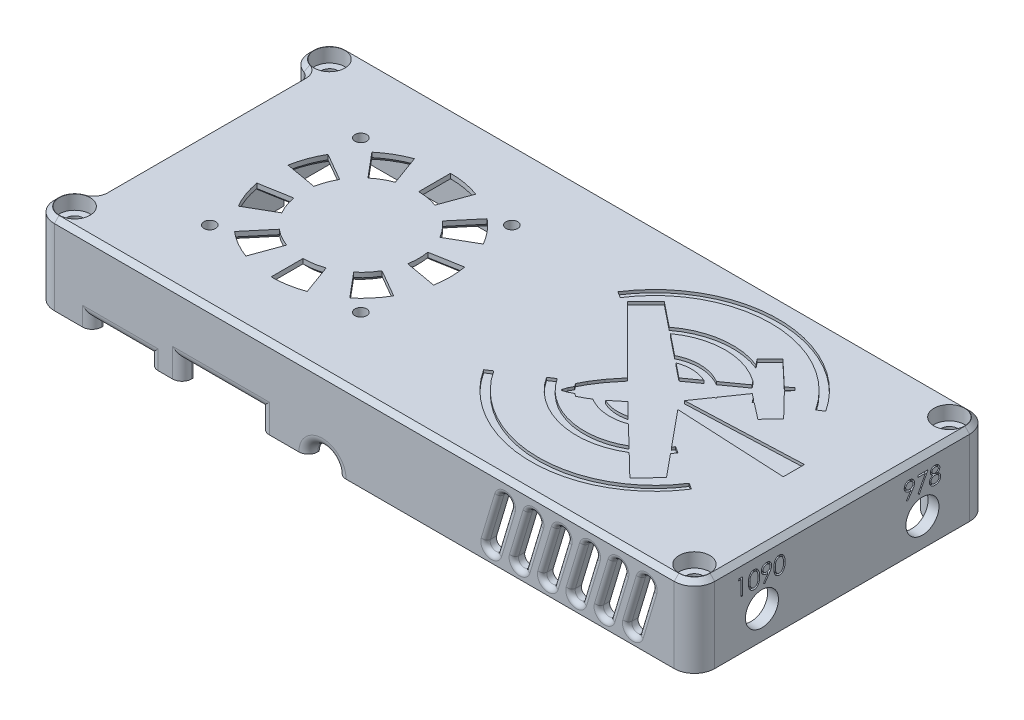
SolidWorks part; units mm, degrees
ref_plane "Front Plane" through (0, 0, 0) normal (0, 0, 1) x (1, 0, 0)
ref_plane "Top Plane" through (0, 0, 0) normal (0, 1, 0) x (1, 0, 0)
ref_plane "Right Plane" through (0, 0, 0) normal (1, 0, 0) x (0, 0, -1)
sketch "Sketch1" plane through (0, 0, 0) normal (0, 1, 0) x (1, 0, 0)
  line L0 (-71.5618, 3.106) -> (57.4382, 3.106) construction
  line L1 (-71.5618, 31.106) -> (57.4382, 31.106)
  line L2 (-71.5618, 31.106) -> (-71.5618, -24.894)
  line L3 (-71.5618, -24.894) -> (57.4382, -24.894)
  line L4 (57.4382, 31.106) -> (57.4382, -24.894)
  line L5 (-60.6618, -24.894) -> (-60.6618, -31.6828) construction
  line L6 (-68.0618, 27.606) -> (-10.0618, 27.606)
  line L7 (-68.0618, 27.606) -> (-68.0618, -21.394)
  line L8 (-68.0618, -21.394) -> (-10.0618, -21.394)
  line L9 (-10.0618, 27.606) -> (-10.0618, -21.394)
  line L10 (-39.5618, -24.894) -> (-39.5618, -31.6828) construction
  line L11 (-18.0618, -24.894) -> (-18.0618, -31.6828) construction
  line L12 (-65.4118, -26.5648) -> (-55.9118, -26.5648) construction
  line L13 (-48.0618, -26.5648) -> (-31.0618, -26.5648) construction
  line L14 (-22.0618, -26.5648) -> (-14.0618, -26.5648) construction
  line L15 (-72.5618, 9.606) -> (-72.5618, -3.394) construction
  line L16 (-71.5618, 3.106) -> (-72.5618, 3.106) construction
  line L17 (-60.6618, -24.894) -> (-60.6618, 40.2849) construction
  dimension "D1" = 129
  dimension "D2" = 56
  dimension "D3" = 49
  dimension "D4" = 58
  dimension "D5" = 3.5
  dimension "D6" = 3.5
  dimension "D7" = 10.9
  dimension "D8" = 32
  dimension "D9" = 53.5
  dimension "D10" = 2
  dimension "D11" = 13
  dimension "D12" = 9.5
  dimension "D13" = 17
  dimension "D14" = 8
sketch "Sketch3" plane through (0, 0, 0) normal (0, 1, 0) x (1, 0, 0)
  line L2 (-72.5618, -25.894) -> (58.4382, -25.894) construction
  line L3 (60.7382, -28.194) -> (60.7382, 34.406) construction
  line L4 (60.7382, 34.406) -> (-74.8618, 34.406)
  line L5 (-74.8618, 34.406) -> (-74.8618, -28.194)
  line L6 (-74.8618, -28.194) -> (60.7382, -28.194)
  line L8 (58.4382, 32.106) -> (-72.5618, 32.106)
  line L9 (58.4382, -25.894) -> (58.4382, 32.106)
  line L10 (-72.5618, -25.894) -> (58.4382, -25.894)
  line L11 (-72.5618, 32.106) -> (-72.5618, -25.894)
  line L12 (58.4382, 32.106) -> (-72.5618, 32.106)
  line L13 (58.4382, -25.894) -> (58.4382, 32.106)
  line L14 (-72.5618, -25.894) -> (58.4382, -25.894)
  line L15 (-72.5618, 32.106) -> (-72.5618, -25.894)
  line L16 (-7.0618, 3.106) -> (-7.0618, 34.406) construction
  line L17 (-71.5618, 3.106) -> (57.4382, 3.106) construction
  line L18 (58.4382, -25.894) -> (58.4382, 32.106) construction
  line L20 (-74.8618, 3.106) -> (52.7382, 3.106) construction
  line L22 (-74.8618, -28.194) -> (60.7382, -28.194) construction
  line L23 (60.7382, -28.194) -> (60.7382, 34.406)
  dimension "D1" = 1
  dimension "D2" = 2.3
extrude "Boss-Extrude1" add sketch "Sketch3" along normal blind 17
sketch "Sketch5" plane through (0, 0, 0) normal (0, 1, 0) x (1, 0, 0)
  line L1 (-72.5618, 32.106) -> (58.4382, 32.106)
  line L2 (-72.5618, 32.106) -> (-72.5618, -25.894)
  line L3 (-72.5618, -25.894) -> (58.4382, -25.894)
  line L4 (58.4382, 32.106) -> (58.4382, -25.894)
sketch "Sketch11" plane through (0, 0, 28.194) normal (0, 0, 1) x (1, 0, 0)
  line L0 (-74.8618, 17) -> (-74.8618, 0) construction
  line L2 (-66.8618, 0) -> (-54.8618, 0)
  line L3 (-66.8618, 0) -> (-66.8618, 2)
  line L4 (-66.8618, 2) -> (-54.8618, 2)
  line L5 (-54.8618, 0) -> (-54.8618, 2)
  line L9 (-47.8118, 4) -> (-31.3118, 4)
  line L10 (-47.8118, 4) -> (-47.8118, 0)
  line L11 (-47.8118, 0) -> (-31.3118, 0)
  line L12 (-31.3118, 4) -> (-31.3118, 0)
  line L14 (-39.5618, 0) -> (-39.528, 10.3) construction
  line L15 (-48.0618, 0) -> (-31.0618, 0) construction
  line L16 (-18.0618, 0) -> (-18.0618, 10.3) construction
  line L17 (-22.0618, 0) -> (-14.0618, 0) construction
  circle A0 centre (-18.0618, 0) radius 3
  dimension "D5" = 6
  dimension "D1" = 4
  dimension "D2" = 2
  dimension "D3" = 12
  dimension "D4" = 16.5
  dimension "D7" = 8
extrude "Cut-Extrude1" cut sketch "Sketch11" against normal up to next
sketch "Sketch14" plane through (0, 0, 0) normal (0, -1, 0) x (1, 0, 0)
  line L1 (-74.8618, 11.894) -> (-72.5618, 11.894)
  line L2 (-74.8618, 11.894) -> (-74.8618, -18.106)
  line L3 (-74.8618, -18.106) -> (-72.5618, -18.106)
  line L4 (-72.5618, 11.894) -> (-72.5618, -18.106)
  dimension "D1" = 30
extrude "Boss-Extrude6" add sketch "Sketch14" along normal blind 2.8
fillet "Fillet6" radius 2 4 edges at (-18.0618, 3, 28.194) (-31.3118, 2, 28.194) (-39.5618, 4, 28.194) (-47.8118, 2, 28.194)
sketch "Sketch15" plane through (-74.8618, 0, 0) normal (-1, 0, 0) x (0, 0, 1)
  line L1 (-9.7403, -3.6489) -> (3.7597, -3.6489)
  line L2 (-9.7403, -3.6489) -> (-9.7403, -2.6489)
  line L3 (-9.7403, -2.6489) -> (3.7597, -2.6489)
  line L4 (3.7597, -3.6489) -> (3.7597, -2.6489)
extrude "Cut-Extrude3" cut sketch "Sketch15" against normal up to next
fillet "Fillet8" radius 2 3 edges at (-74.8618, -2.7245, 3.7597) (-74.8618, -2.7245, -9.7403) (-74.8618, -2.6489, -2.9903)
sketch "Sketch35" plane through (0, 17, 0) normal (0, 1, 0) x (1, 0, 0)
  line L1 (-72.5618, 32.106) -> (58.4382, 32.106)
  line L2 (-72.5618, 32.106) -> (-72.5618, -25.894)
  line L3 (-72.5618, -25.894) -> (58.4382, -25.894)
  line L4 (58.4382, 32.106) -> (58.4382, -25.894)
extrude "Boss-Extrude7" add sketch "Sketch35" against normal blind 2
sketch "Sketch36" plane through (0, 17, 0) normal (0, 1, 0) x (1, 0, 0)
  line L0 (13.7863, -0.484) -> (12.349, -1.4216)
  line L1 (26.8986, -0.4563) -> (28.3399, -1.3879)
  line L2 (13.7684, 8.0304) -> (12.3271, 8.962)
  line L3 (26.8807, 8.058) -> (28.318, 8.9957)
  line L4 (41.0203, -9.5839) -> (42.3245, -10.4269)
  line L5 (32.8559, -4.3068) -> (34.2397, -5.2013)
  line L6 (7.8454, -4.3595) -> (6.4653, -5.2598)
  line L7 (-0.2967, -9.6709) -> (-1.5974, -10.5194)
  line L8 (-0.3532, 17.158) -> (-1.6575, 18.001)
  line L9 (7.8112, 11.8809) -> (6.4273, 12.7754)
  line L10 (32.8217, 11.9336) -> (34.2017, 12.8338)
  line L11 (40.9638, 17.245) -> (42.2645, 18.0935)
  line L12 (49.7971, 1.5668) -> (22.6747, 2.9133)
  line L13 (49.7971, 6.0552) -> (22.6747, 4.9652)
  line L14 (49.7971, 1.5668) -> (49.7971, 6.0552)
  line L15 (22.6747, 2.9133) -> (22.6747, 4.9652)
  arc A0 (42.2645, 18.0935) -> (-1.6575, 18.001) centre (20.3335, 3.787) ccw
  arc A1 (40.9638, 17.245) -> (-0.3532, 17.158) centre (20.3335, 3.787) ccw
  arc A2 (26.8807, 8.058) -> (13.7684, 8.0304) centre (20.3335, 3.787) ccw
  arc A3 (28.318, 8.9957) -> (12.3271, 8.962) centre (20.3335, 3.787) ccw
  arc A4 (34.2017, 12.8338) -> (6.4273, 12.7754) centre (20.3335, 3.787) ccw
  arc A5 (32.8217, 11.9336) -> (7.8112, 11.8809) centre (20.3335, 3.787) ccw
  arc A6 (-1.5974, -10.5194) -> (42.3245, -10.4269) centre (20.3335, 3.787) ccw
  arc A7 (-0.2967, -9.6709) -> (41.0203, -9.5839) centre (20.3335, 3.787) ccw
  arc A8 (6.4653, -5.2598) -> (34.2397, -5.2013) centre (20.3335, 3.787) ccw
  arc A9 (7.8454, -4.3595) -> (32.8559, -4.3068) centre (20.3335, 3.787) ccw
  arc A10 (12.349, -1.4216) -> (28.3399, -1.3879) centre (20.3335, 3.787) ccw
  arc A11 (13.7863, -0.484) -> (26.8986, -0.4563) centre (20.3335, 3.787) ccw
extrude "Cut-Extrude4" cut sketch "Sketch36" against normal blind 0.6
sketch "Sketch37" plane through (0, 17, 0) normal (0, 1, 0) x (1, 0, 0)
  line L0 (19.5432, -1.113) -> (33.7651, -14.904)
  line L1 (33.7651, -14.904) -> (37.5849, -10.9649)
  line L2 (37.5849, -10.9649) -> (24.9049, 4.4162)
  line L3 (24.9049, 4.4162) -> (31.2449, 13.5399)
  line L4 (31.2449, 13.5399) -> (36.5589, 9.4198)
  line L5 (36.5589, 9.4198) -> (39.2481, 12.193)
  line L6 (39.2481, 12.193) -> (34.218, 17.3746)
  line L7 (34.218, 17.3746) -> (35.2171, 18.6632)
  line L8 (35.2171, 18.6632) -> (34.9302, 18.8856)
  line L9 (19.5432, -1.113) -> (16.9215, -3.2743)
  line L10 (16.9215, -3.2743) -> (14.6893, -4.7957)
  line L11 (14.6893, -4.7957) -> (13.0543, -5.6738)
  line L12 (13.0543, -5.6738) -> (12.4225, -5.2348)
  line L13 (12.4225, -5.2348) -> (11.4673, -5.7477)
  line L14 (11.4673, -5.7477) -> (10.605, -6.0351)
  line L15 (10.605, -6.0351) -> (10.3641, -6.0351)
  line L16 (34.9302, 18.8856) -> (10.3641, -6.0351) construction
  line L17 (10.3607, -5.7943) -> (10.3641, -6.0351)
  line L18 (10.6357, -4.9279) -> (10.3607, -5.7943)
  line L19 (11.1349, -3.9655) -> (10.6357, -4.9279)
  line L20 (10.6869, -3.3401) -> (11.1349, -3.9655)
  line L21 (11.5414, -1.6927) -> (10.6869, -3.3401)
  line L22 (13.0306, 0.5611) -> (11.5414, -1.6927)
  line L23 (15.1541, 3.2135) -> (13.0306, 0.5611)
  line L24 (34.7036, 19.1694) -> (34.9302, 18.8856)
  line L25 (33.4295, 18.1519) -> (34.7036, 19.1694)
  line L26 (28.1763, 23.1072) -> (33.4295, 18.1519)
  line L27 (25.4419, 20.3785) -> (28.1763, 23.1072)
  line L28 (29.6378, 15.1241) -> (25.4419, 20.3785)
  line L29 (20.6059, 8.6539) -> (29.6378, 15.1241)
  line L30 (5.0446, 21.1121) -> (20.6059, 8.6539)
  line L31 (1.1607, 17.2363) -> (5.0446, 21.1121)
  line L32 (15.1541, 3.2135) -> (1.1607, 17.2363)
extrude "Cut-Extrude5" cut sketch "Sketch37" against normal blind 0.6
sketch "Sketch48" plane through (0, 17, 0) normal (0, 1, 0) x (1, 0, 0)
  line L0 (-74.8618, -19.594) -> (-74.8618, -28.194)
  line L1 (-74.8618, 34.406) -> (-74.8618, 25.806)
  line L2 (-74.8618, 3.106) -> (-35.5735, 3.106) construction
  line L3 (-74.8618, 34.406) -> (-74.8618, -28.194) construction
  line L4 (60.7382, -28.194) -> (60.7382, 34.406) construction
  arc A0 (-74.8618, -28.194) -> (-74.8618, -19.594) centre (-74.8618, -23.894) cw
  arc A1 (-74.8618, 25.806) -> (-74.8618, 34.406) centre (-74.8618, 30.106) cw
  circle A2 centre (56.4382, 30.106) radius 4.3
  circle A3 centre (56.4382, -23.894) radius 4.3
  dimension "D1" = 4.3
extrude "Boss-Extrude9" add sketch "Sketch48" against normal up to vertex (17 mm away) up to point (-74.8618, 0, -34.406)
hole_wizard "CBORE for M3 SHCS1" positions "Sketch50" profile "Sketch49" counterbore size "M3" standard "ANSI Metric" end condition up to next
sketch "Sketch50" plane through (0, 17, 0) normal (0, 1, 0) x (1, 0, 0)
  point P0 (-74.8618, 30.106)
sketch "Sketch49" plane through (-74.8618, 17, -30.106) normal (1, 0, 0) x (0, 0, 1)
  line L0 (0, 0) -> (0, 17)
  line L1 (0, 17) -> (1.8, 17)
  line L3 (1.8, 17) -> (1.8, 3)
  line L4 (1.8, 3) -> (3.25, 3)
  line L5 (3.25, 3) -> (3.25, 0)
  line L7 (3.25, 0) -> (0, 0)
  line L11 (0, -6.35) -> (0, 107.95) construction
  dimension "Thru Hole Dia." = 3.6
  dimension "Thru Hole Depth" = 17
  dimension "C'Bore Dia." = 6.5
  dimension "C'Bore Depth" = 3
hole_wizard "CBORE for M3 SHCS2" positions "Sketch52" profile "Sketch51" counterbore size "M3" standard "ANSI Metric" end condition up to next
sketch "Sketch52" plane through (0, 17, 0) normal (0, 1, 0) x (1, 0, 0)
  point P0 (-74.8618, -23.894)
sketch "Sketch51" plane through (-74.8618, 17, 23.894) normal (1, 0, 0) x (0, 0, 1)
  line L0 (0, 0) -> (0, 17)
  line L1 (0, 17) -> (1.8, 17)
  line L3 (1.8, 17) -> (1.8, 3)
  line L4 (1.8, 3) -> (3.25, 3)
  line L5 (3.25, 3) -> (3.25, 0)
  line L7 (3.25, 0) -> (0, 0)
  line L11 (0, -6.35) -> (0, 107.95) construction
  dimension "Thru Hole Dia." = 3.6
  dimension "Thru Hole Depth" = 17
  dimension "C'Bore Dia." = 6.5
  dimension "C'Bore Depth" = 3
fillet "Fillet13" radius 2 2 edges at (-74.8618, 8.5, 19.594) (-74.8618, 8.5, -25.806)
chamfer "Chamfer1" distance 1 angle 45 1 edges at (-9.8342, 15, -32.106)
chamfer "Chamfer3" distance 1 angle 45 7 edges at (-7.0618, 17, 28.194) (-79.1058, 17, 24.5855) (-75.2385, 17, 19.0883) (-74.8618, 17, -3.106) (-75.2385, 17, -25.3002) (-79.1058, 17, -30.7975) (-7.0618, 17, -34.406)
fillet "Fillet14" radius 2 3 edges at (-66.8618, 1, 28.194) (-60.8618, 2, 28.194) (-54.8618, 1, 28.194)
fillet "Fillet15" radius 4.3 2 edges at (60.7382, 8, -34.406) (60.7382, 8, 28.194)
hole_wizard "CBORE for M3 SHCS4" positions "Sketch62" profile "Sketch61" counterbore size "M3" standard "ANSI Metric" end condition up to next
sketch "Sketch62" plane through (0, 17, 0) normal (0, 1, 0) x (1, 0, 0)
  point P0 (56.4382, 30.106)
sketch "Sketch61" plane through (56.4382, 17, -30.106) normal (1, 0, 0) x (0, 0, 1)
  line L0 (0, 0) -> (0, 17)
  line L1 (0, 17) -> (1.8, 17)
  line L3 (1.8, 17) -> (1.8, 3)
  line L4 (1.8, 3) -> (3.25, 3)
  line L5 (3.25, 3) -> (3.25, 0)
  line L7 (3.25, 0) -> (0, 0)
  line L11 (0, -6.35) -> (0, 107.95) construction
  dimension "Thru Hole Dia." = 3.6
  dimension "Thru Hole Depth" = 17
  dimension "C'Bore Dia." = 6.5
  dimension "C'Bore Depth" = 3
hole_wizard "CBORE for M3 SHCS5" positions "Sketch64" profile "Sketch63" counterbore size "M3" standard "ANSI Metric" end condition up to next
sketch "Sketch64" plane through (0, 17, 0) normal (0, 1, 0) x (1, 0, 0)
  point P0 (56.4382, -23.894)
sketch "Sketch63" plane through (56.4382, 17, 23.894) normal (1, 0, 0) x (0, 0, 1)
  line L0 (0, 0) -> (0, 17)
  line L1 (0, 17) -> (1.8, 17)
  line L3 (1.8, 17) -> (1.8, 3)
  line L4 (1.8, 3) -> (3.25, 3)
  line L5 (3.25, 3) -> (3.25, 0)
  line L7 (3.25, 0) -> (0, 0)
  line L11 (0, -6.35) -> (0, 107.95) construction
  dimension "Thru Hole Dia." = 3.6
  dimension "Thru Hole Depth" = 17
  dimension "C'Bore Dia." = 6.5
  dimension "C'Bore Depth" = 3
chamfer "Chamfer7" distance 1 angle 45 3 edges at (60.3334, 17, 25.7155) (60.3334, 17, -31.9275) (60.7382, 17, -3.106)
sketch "Sketch67" plane through (0, 0, 28.194) normal (0, 0, 1) x (1, 0, 0)
  line L0 (44.5955, 12.4849) -> (41.7225, 2.9065) construction
  line L1 (45.7928, 12.1258) -> (42.9198, 2.5474)
  line L2 (43.3981, 12.8441) -> (40.5252, 3.2656)
  line L3 (38.5955, 12.4849) -> (35.7225, 2.9065) construction
  line L4 (39.7928, 12.1258) -> (36.9198, 2.5474)
  line L5 (37.3981, 12.8441) -> (34.5252, 3.2656)
  line L6 (32.5955, 12.4849) -> (29.7225, 2.9065) construction
  line L7 (33.7928, 12.1258) -> (30.9198, 2.5474)
  line L8 (31.3981, 12.8441) -> (28.5252, 3.2656)
  line L9 (26.5955, 12.4849) -> (23.7225, 2.9065) construction
  line L10 (27.7928, 12.1258) -> (24.9198, 2.5474)
  line L11 (25.3981, 12.8441) -> (22.5252, 3.2656)
  line L12 (50.5955, 12.4849) -> (47.7225, 2.9065) construction
  line L13 (51.7928, 12.1258) -> (48.9198, 2.5474)
  line L14 (49.3981, 12.8441) -> (46.5252, 3.2656)
  line L15 (20.5955, 12.4849) -> (17.7225, 2.9065) construction
  line L16 (21.7928, 12.1258) -> (18.9198, 2.5474)
  line L17 (19.3981, 12.8441) -> (16.5252, 3.2656)
  arc A0 (45.7928, 12.1258) -> (43.3981, 12.8441) centre (44.5955, 12.4849) ccw
  arc A1 (40.5252, 3.2656) -> (42.9198, 2.5474) centre (41.7225, 2.9065) ccw
  arc A2 (39.7928, 12.1258) -> (37.3981, 12.8441) centre (38.5955, 12.4849) ccw
  arc A3 (34.5252, 3.2656) -> (36.9198, 2.5474) centre (35.7225, 2.9065) ccw
  arc A4 (33.7928, 12.1258) -> (31.3981, 12.8441) centre (32.5955, 12.4849) ccw
  arc A5 (28.5252, 3.2656) -> (30.9198, 2.5474) centre (29.7225, 2.9065) ccw
  arc A6 (27.7928, 12.1258) -> (25.3981, 12.8441) centre (26.5955, 12.4849) ccw
  arc A7 (22.5252, 3.2656) -> (24.9198, 2.5474) centre (23.7225, 2.9065) ccw
  arc A8 (51.7928, 12.1258) -> (49.3981, 12.8441) centre (50.5955, 12.4849) ccw
  arc A9 (46.5252, 3.2656) -> (48.9198, 2.5474) centre (47.7225, 2.9065) ccw
  arc A10 (21.7928, 12.1258) -> (19.3981, 12.8441) centre (20.5955, 12.4849) ccw
  arc A11 (16.5252, 3.2656) -> (18.9198, 2.5474) centre (17.7225, 2.9065) ccw
  point P3 (43.159, 7.6957)
  point P10 (37.159, 7.6957)
  point P17 (31.159, 7.6957)
  point P24 (25.159, 7.6957)
  point P30 (49.159, 7.6957)
  point P38 (19.159, 7.6957)
  dimension "D1" = 6
sketch "Sketch68" plane through (60.7382, 0, 0) normal (1, 0, 0) x (0, 0, -1)
  line L0 (-23.894, 6) -> (30.106, 6) construction
  line L1 (-23.894, 16) -> (-23.894, 0) construction
  line L2 (30.106, 0) -> (30.106, 16) construction
  line L3 (-23.894, 0) -> (30.106, 0) construction
  circle A0 centre (-13.894, 6) radius 3.5
  circle A1 centre (20.106, 6) radius 3.5
  dimension "D1" = 10
  dimension "D2" = 10
  dimension "D3" = 6
extrude "Cut-Extrude19" cut sketch "Sketch68" against normal up to next
sketch "Sketch69" plane through (60.7382, 0, 0) normal (1, 0, 0) x (0, 0, -1)
  line L0 (-19.5849, 10.4138) -> (-8.2031, 10.4138) construction
  line L1 (14.0086, 10.4138) -> (26.2034, 10.4138) construction
  text T0 "1090"
  text T1 "978"
extrude "Cut-Extrude20" cut sketch "Sketch69" against normal blind 0.5
extrude "Cut-Extrude22" cut sketch "Sketch67" against normal through all
fillet "Fillet17" radius 1 48 edges at (50.9546, 13.6822, -34.406) (50.3563, 7.3366, -34.406) (47.3633, 1.7092, -34.406) (50.9546, 13.6822, 28.194) (50.3563, 7.3366, 28.194) (47.3633, 1.7092, 28.194) (47.9617, 8.0548, -34.406) (47.9617, 8.0548, 28.194) (44.9546, 13.6822, -34.406) (44.3563, 7.3366, -34.406) (41.3633, 1.7092, -34.406) (38.9546, 13.6822, -34.406) (38.3563, 7.3366, -34.406) (35.3633, 1.7092, -34.406) (32.9546, 13.6822, -34.406) (32.3563, 7.3366, -34.406) (29.3633, 1.7092, -34.406) (26.9546, 13.6822, -34.406) (26.3563, 7.3366, -34.406) (23.3633, 1.7092, -34.406) (20.9546, 13.6822, -34.406) (20.3563, 7.3366, -34.406) (17.3633, 1.7092, -34.406) (44.9546, 13.6822, 28.194) (44.3563, 7.3366, 28.194) (41.3633, 1.7092, 28.194) (38.9546, 13.6822, 28.194) (38.3563, 7.3366, 28.194) (35.3633, 1.7092, 28.194) (32.9546, 13.6822, 28.194) (32.3563, 7.3366, 28.194) (29.3633, 1.7092, 28.194) (26.9546, 13.6822, 28.194) (26.3563, 7.3366, 28.194) (23.3633, 1.7092, 28.194) (20.9546, 13.6822, 28.194) (20.3563, 7.3366, 28.194) (17.3633, 1.7092, 28.194) (41.9617, 8.0548, -34.406) (35.9617, 8.0548, -34.406) (29.9617, 8.0548, -34.406) (23.9617, 8.0548, -34.406) (17.9617, 8.0548, -34.406) (41.9617, 8.0548, 28.194) (35.9617, 8.0548, 28.194) (29.9617, 8.0548, 28.194) (23.9617, 8.0548, 28.194) (17.9617, 8.0548, 28.194)
sketch "Sketch70" plane through (0, 15, 0) normal (0, -1, 0) x (1, 0, 0)
  line L0 (-41.126, 16.0097) -> (-41.126, 9.2698)
  line L1 (-34.6276, 14.8639) -> (-36.9328, 8.5304)
  line L2 (-28.913, 11.5645) -> (-33.2454, 6.4015)
  line L3 (-24.6715, 6.5097) -> (-30.5085, 3.1397)
  line L4 (-22.4146, 0.309) -> (-29.0522, -0.8614)
  line L5 (-22.4146, -6.2896) -> (-29.0522, -5.1192)
  line L6 (-24.6715, -12.4903) -> (-30.5085, -9.1203)
  line L7 (-28.913, -17.5451) -> (-33.2454, -12.3821)
  line L8 (-34.6276, -20.8445) -> (-36.9328, -14.511)
  line L9 (-41.126, -21.9903) -> (-41.126, -15.2504)
  line L10 (-47.6244, -20.8445) -> (-45.3192, -14.511)
  line L11 (-53.339, -17.5451) -> (-49.0066, -12.3821)
  line L12 (-57.5805, -12.4903) -> (-51.7435, -9.1203)
  line L13 (-59.8373, -6.2896) -> (-53.1998, -5.1192)
  line L14 (-59.8373, 0.309) -> (-53.1998, -0.8614)
  line L15 (-57.5805, 6.5097) -> (-51.7435, 3.1397)
  line L16 (-53.339, 11.5645) -> (-49.0066, 6.4015)
  line L17 (-47.6244, 14.8639) -> (-45.3192, 8.5304)
  line L19 (-57.126, -18.9903) -> (-25.126, -18.9903) construction
  line L20 (-57.126, -18.9903) -> (-57.126, 13.0097) construction
  line L21 (-57.126, 13.0097) -> (-25.126, 13.0097) construction
  line L22 (-25.126, -18.9903) -> (-25.126, 13.0097) construction
  line L23 (-57.126, -18.9903) -> (-25.126, 13.0097) construction
  line L24 (-57.126, 13.0097) -> (-25.126, -18.9903) construction
  arc A0 (-34.6276, 14.8639) -> (-41.126, 16.0097) centre (-41.126, -2.9903) ccw
  arc A1 (-36.9328, 8.5304) -> (-41.126, 9.2698) centre (-41.126, -2.9903) ccw
  arc A2 (-24.6715, 6.5097) -> (-28.913, 11.5645) centre (-41.126, -2.9903) ccw
  arc A3 (-30.5085, 3.1397) -> (-33.2454, 6.4015) centre (-41.126, -2.9903) ccw
  arc A4 (-22.4146, -6.2896) -> (-22.4146, 0.309) centre (-41.126, -2.9903) ccw
  arc A5 (-29.0522, -5.1192) -> (-29.0522, -0.8614) centre (-41.126, -2.9903) ccw
  arc A6 (-28.913, -17.5451) -> (-24.6715, -12.4903) centre (-41.126, -2.9903) ccw
  arc A7 (-33.2454, -12.3821) -> (-30.5085, -9.1203) centre (-41.126, -2.9903) ccw
  arc A8 (-41.126, -21.9903) -> (-34.6276, -20.8445) centre (-41.126, -2.9903) ccw
  arc A9 (-41.126, -15.2504) -> (-36.9328, -14.511) centre (-41.126, -2.9903) ccw
  arc A10 (-53.339, -17.5451) -> (-47.6244, -20.8445) centre (-41.126, -2.9903) ccw
  arc A11 (-49.0066, -12.3821) -> (-45.3192, -14.511) centre (-41.126, -2.9903) ccw
  arc A12 (-53.1998, -5.1192) -> (-51.7435, -9.1203) centre (-41.126, -2.9903) ccw
  arc A13 (-59.8373, -6.2896) -> (-57.5805, -12.4903) centre (-41.126, -2.9903) ccw
  arc A14 (-57.5805, 6.5097) -> (-59.8373, 0.309) centre (-41.126, -2.9903) ccw
  arc A15 (-51.7435, 3.1397) -> (-53.1998, -0.8614) centre (-41.126, -2.9903) ccw
  arc A16 (-45.3192, 8.5304) -> (-49.0066, 6.4015) centre (-41.126, -2.9903) ccw
  arc A17 (-47.6244, 14.8639) -> (-53.339, 11.5645) centre (-41.126, -2.9903) ccw
  circle A18 centre (-25.126, 13.0097) radius 1.25
  circle A19 centre (-25.126, -18.9903) radius 1.25
  circle A20 centre (-57.126, -18.9903) radius 1.25
  circle A21 centre (-57.126, 13.0097) radius 1.25
  point P41 (-41.126, -2.9903)
  dimension "D1" = 18
  dimension "D2" = 32
  dimension "D3" = 32
extrude "Cut-Extrude23" cut sketch "Sketch70" against normal up to next
chamfer "Chamfer8" distance 1 angle 45 36 edges at (-35.7802, 15, -17.6777) (-38.9971, 15, -15.0641) (-41.126, 15, -18.6203) (-37.8267, 15, -21.7016) (-27.59, 15, -10.8053) (-31.7342, 15, -10.8709) (-31.0792, 15, -14.9636) (-26.5711, 15, -15.2033) (-25.7334, 15, -0.2762) (-28.8659, 15, -2.9903) (-25.7334, 15, -5.7044) (-22.126, 15, -2.9903) (-27.59, 15, 4.8247) (-31.7342, 15, 4.8903) (-31.0792, 15, 8.983) (-26.5711, 15, 9.2227) (-35.7802, 15, 11.6971) (-38.9971, 15, 9.0835) (-41.126, 15, 12.6397) (-37.8267, 15, 15.721) (-46.4718, 15, 11.6971) (-47.256, 15, 7.6272) (-51.1728, 15, 8.983) (-50.626, 15, 13.4642) (-54.662, 15, 4.8247) (-52.6467, 15, 1.2029) (-56.5186, 15, -0.2762) (-58.9801, 15, 3.5081) (-54.662, 15, -10.8053) (-52.6467, 15, -7.1835) (-56.5186, 15, -5.7044) (-58.9801, 15, -9.4887) (-46.4718, 15, -17.6777) (-47.256, 15, -13.6078) (-51.1728, 15, -14.9636) (-50.626, 15, -19.4448)
